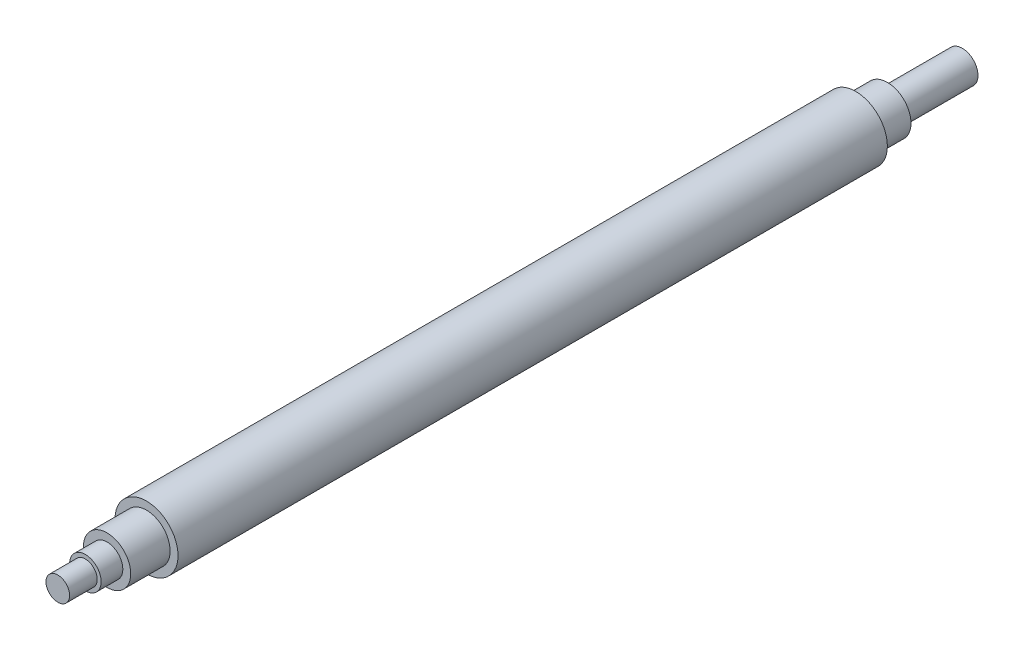
SolidWorks part; units mm, degrees
ref_plane "Piano frontale" through (0, 0, 0) normal (0, 0, 1) x (1, 0, 0)
ref_plane "Piano superiore" through (0, 0, 0) normal (0, 1, 0) x (1, 0, 0)
ref_plane "Piano destro" through (0, 0, 0) normal (1, 0, 0) x (0, 0, -1)
sketch "Schizzo2" plane through (0, 0, 0) normal (1, 0, 0) x (0, 0, -1)
  line L0 (1.5, 0) -> (1.5, 3)
  line L1 (1.5, 3) -> (8.5, 3)
  line L2 (8.5, 3) -> (8.5, 4)
  line L3 (8.5, 4) -> (14, 4)
  line L4 (14, 4) -> (14, 6)
  line L5 (14, 6) -> (24, 6)
  line L6 (24, 6) -> (24, 8)
  line L7 (24, 8) -> (204, 8)
  line L8 (204, 8) -> (204, 6)
  line L9 (204, 6) -> (212, 6)
  line L10 (212, 6) -> (212, 4)
  line L11 (231, 0) -> (1.5, 0)
  line L14 (231, 0) -> (231, 4)
  line L15 (0, 0) -> (351.0218, 0) construction
  line L18 (212, 4) -> (231, 4)
  point P33 (0, 0)
  dimension "D2" = 6
  dimension "D3" = 8
  dimension "D4" = 12
  dimension "D5" = 16
  dimension "D6" = 12
  dimension "D7" = 8
  dimension "D8" = 7
  dimension "D9" = 5.5
  dimension "D10" = 10
  dimension "D11" = 180
  dimension "D12" = 8
  dimension "D13" = 19
revolve "Rivoluzione2" add sketch "Schizzo2" angle 360 about L15
